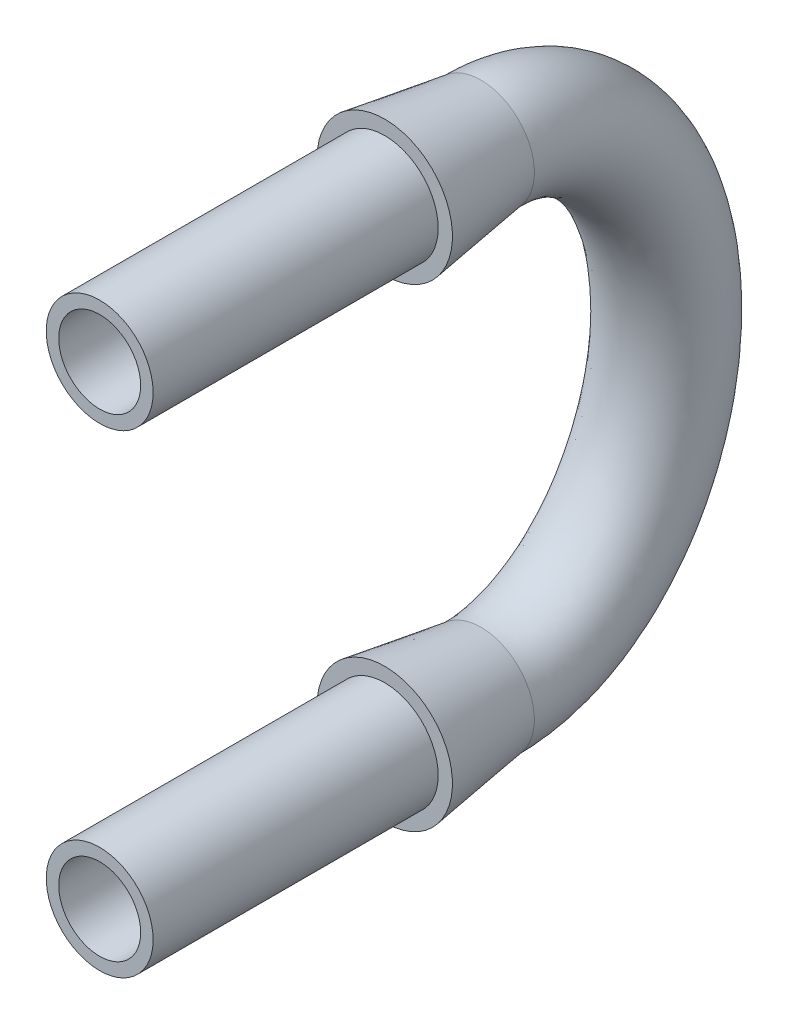
SolidWorks part; units mm, degrees
material "ABS"
ref_plane "Front Plane" through (0, 0, 0) normal (0, 0, 1) x (1, 0, 0)
ref_plane "Top Plane" through (0, 0, 0) normal (0, 1, 0) x (1, 0, 0)
ref_plane "Right Plane" through (0, 0, 0) normal (1, 0, 0) x (0, 0, -1)
sketch "Sketch1" plane through (0, 0, 0) normal (0, 0, 1) x (1, 0, 0)
  circle A0 centre (0, 0) radius 5.75
  circle A1 centre (0, 0) radius 7.5
  dimension "D1" = 11.5
  dimension "D2" = 15
extrude "Boss-Extrude3" add sketch "Sketch1" against normal blind 43.5
sketch "Sketch4" plane through (0, 0, 0) normal (1, 0, 0) x (0, 0, -1)
  line L0 (43.5, 7.5) -> (30, 7.5)
  line L1 (43.5, 7.5) -> (0, 7.5) construction
  line L2 (30, 7.5) -> (30, 9.5)
  line L3 (30, 9.5) -> (43.5, 7.5)
  line L4 (43.5, 0) -> (35.8898, 0)
  line L5 (43.5, -7.5) -> (43.5, 7.5) construction
  dimension "D1" = 13.5
  dimension "D2" = 2
revolve "Revolve1" add sketch "Sketch4" angle 360 about L4
sketch3d "3DSketch1"
  line L2 (0, 33.25, -43.5) -> (0, 33.25, -23.0374)
  line L3 (0, 33.25, -23.0374) -> (21.4772, 33.25, -23.0374)
ref_plane "Plane1" through (0, 33.25, 0) normal (0, -1, 0) x (-1, 0, 0)
sketch "Sketch7" plane through (0, 0, -43.5) normal (0, 0, -1) x (-1, 0, 0)
  circle A0 centre (0, 0) radius 5.75
  circle A1 centre (0, 0) radius 7.5
  circle A2 centre (0, 0) radius 7.5
  dimension "D1" = 0
sketch "Sketch8" plane through (0, 0, 0) normal (1, 0, 0) x (0, 0, -1)
  line L4 (43.5, -7.5) -> (43.5, 7.5) construction
  ellipse E0 centre (43.5, 33.25) end of major axis (43.5, 0) minor radius 26 (43.5, 0) -> (43.5, 66.5) ccw
mirror "Mirror5" about plane through (0, 33.25, 0) normal (0, -1, 0) of bodies 104
sweep "Sweep13" add profiles "Sketch7" path "Sketch8"
sketch "Sketch10" plane through (0, 0, 0) normal (0, 0, 1) x (1, 0, 0)
  circle A0 centre (0, 0) radius 5.75
  circle A1 centre (0, 0) radius 7.5
  circle A2 centre (0, 0) radius 7.5
  circle A3 centre (0, 66.5) radius 5.75
  circle A4 centre (0, 66.5) radius 7.5
  dimension "D1" = 0
extrude "Boss-Extrude4" add sketch "Sketch10" along normal blind 10
